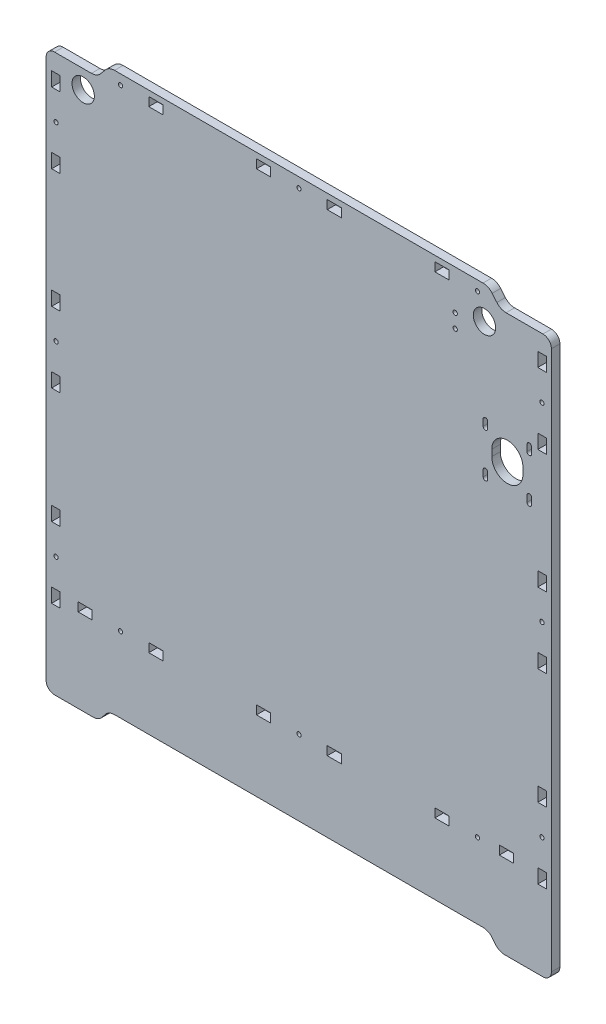
SolidWorks part; units mm, degrees
ref_plane "Спереди" through (0, 0, 0) normal (0, 0, 1) x (1, 0, 0)
ref_plane "Сверху" through (0, 0, 0) normal (0, 1, 0) x (1, 0, 0)
ref_plane "Справа" through (0, 0, 0) normal (1, 0, 0) x (0, 0, -1)
sketch "Эскиз1" plane through (0, 0, 0) normal (0, 0, 1) x (1, 0, 0)
  line L0 (133.6555, 83.4698) -> (133.6555, 87.9698)
  line L1 (133.6555, 118.9698) -> (133.6555, 114.4698)
  line L2 (130.4555, 83.4698) -> (130.4555, 87.9698)
  line L3 (158.5555, 98.9698) -> (158.5555, 103.4698)
  line L4 (130.4555, 118.9698) -> (130.4555, 114.4698)
  line L5 (161.4555, 118.9698) -> (161.4555, 114.4698)
  line L6 (164.6555, 118.9698) -> (164.6555, 114.4698)
  line L7 (136.5555, 98.9698) -> (136.5555, 103.4698)
  line L8 (161.4555, 83.4698) -> (161.4555, 87.9698)
  line L9 (164.6555, 83.4698) -> (164.6555, 87.9698)
  line L10 (-174.3451, 35.4216) -> (-174.3451, 45.4216)
  line L11 (106.3726, -142.2004) -> (96.3778, -142.2004)
  line L12 (96.3778, -142.2004) -> (96.3778, -136.0006)
  line L13 (96.3778, -136.0006) -> (106.3726, -136.0006)
  line L14 (106.3726, -136.0006) -> (106.3726, -142.2004)
  line L15 (151.7592, -142.2004) -> (141.91, -142.2004)
  line L16 (141.91, -142.2004) -> (141.91, -136.0006)
  line L17 (141.91, -136.0006) -> (151.7592, -136.0006)
  line L18 (151.7592, -136.0006) -> (151.7592, -142.2004)
  line L19 (-19.7199, 191.9054) -> (-29.6916, 191.9054)
  line L20 (-29.6916, 191.9054) -> (-29.6916, 198.1051)
  line L21 (-29.6916, 198.1051) -> (-19.7199, 198.1051)
  line L22 (-19.7199, 198.1051) -> (-19.7199, 191.9054)
  line L23 (30.2801, 191.9054) -> (20.3037, 191.9054)
  line L24 (20.3037, 191.9054) -> (20.3037, 198.1051)
  line L25 (20.3037, 198.1051) -> (30.2801, 198.1051)
  line L26 (30.2801, 198.1051) -> (30.2801, 191.9054)
  line L27 (-145.8164, -142.2004) -> (-155.6656, -142.2004)
  line L28 (-155.6656, -142.2004) -> (-155.6656, -136.0006)
  line L29 (-155.6656, -136.0006) -> (-145.8164, -136.0006)
  line L30 (-145.8164, -136.0006) -> (-145.8164, -142.2004)
  line L31 (-95.8164, -142.2004) -> (-105.7664, -142.2004)
  line L32 (-105.7664, -142.2004) -> (-105.7664, -136.0006)
  line L33 (-105.7664, -136.0006) -> (-95.8164, -136.0006)
  line L34 (-95.8164, -136.0006) -> (-95.8164, -142.2004)
  line L35 (-19.722, -142.199) -> (-29.6916, -142.199)
  line L36 (-29.6916, -142.199) -> (-29.6916, -135.9992)
  line L37 (-29.6916, -135.9992) -> (-19.722, -135.9992)
  line L38 (-19.722, -135.9992) -> (-19.722, -142.199)
  line L39 (30.2781, -142.199) -> (20.3037, -142.199)
  line L40 (20.3037, -142.199) -> (20.3037, -135.9992)
  line L41 (20.3037, -135.9992) -> (30.2781, -135.9992)
  line L42 (30.2781, -135.9992) -> (30.2781, -142.199)
  line L43 (-174.3451, 45.4216) -> (-168.4387, 45.4216)
  line L44 (-168.4387, 45.4216) -> (-168.4387, 35.4216)
  line L45 (-168.4387, 35.4216) -> (-174.3451, 35.4216)
  line L46 (-174.4387, -14.5784) -> (-174.4387, -4.5784)
  line L47 (-174.4387, -4.5784) -> (-168.4387, -4.5784)
  line L48 (-168.4387, -4.5784) -> (-168.4387, -14.5784)
  line L49 (-168.4387, -14.5784) -> (-174.4387, -14.5784)
  line L50 (-174.3451, 169.5931) -> (-174.3451, 179.5931)
  line L51 (-174.3451, 179.5931) -> (-168.4387, 179.5931)
  line L52 (-168.4387, 179.5931) -> (-168.4387, 169.5931)
  line L53 (-168.4387, 169.5931) -> (-174.3451, 169.5931)
  line L54 (-174.3451, 119.5932) -> (-174.3451, 129.5932)
  line L55 (-174.3451, 129.5932) -> (-168.4387, 129.5932)
  line L56 (-168.4387, 129.5932) -> (-168.4387, 119.5932)
  line L57 (-168.4387, 119.5932) -> (-174.3451, 119.5932)
  line L58 (-174.4387, -96.2996) -> (-174.4387, -86.2996)
  line L59 (-174.4387, -86.2996) -> (-168.4387, -86.2996)
  line L60 (-168.4387, -86.2996) -> (-168.4387, -96.2996)
  line L61 (-168.4387, -96.2996) -> (-174.4387, -96.2996)
  line L62 (-174.4387, -146.2996) -> (-174.4387, -136.2996)
  line L63 (-174.4387, -136.2996) -> (-168.4387, -136.2996)
  line L64 (-168.4387, -136.2996) -> (-168.4387, -146.2996)
  line L65 (-168.4387, -146.2996) -> (-174.4387, -146.2996)
  line L66 (169.0555, 35.4216) -> (169.0555, 45.4216)
  line L67 (169.0555, 45.4216) -> (175.077, 45.4216)
  line L68 (175.077, 45.4216) -> (175.077, 35.4216)
  line L69 (175.077, 35.4216) -> (169.0555, 35.4216)
  line L70 (169.0555, -14.5784) -> (169.0555, -4.5784)
  line L71 (169.0555, -4.5784) -> (175.077, -4.5784)
  line L72 (175.077, -4.5784) -> (175.077, -14.5784)
  line L73 (175.077, -14.5784) -> (169.0555, -14.5784)
  line L74 (169.0555, -96.2996) -> (169.0555, -86.2996)
  line L75 (169.0555, -86.2996) -> (175.077, -86.2996)
  line L76 (175.077, -86.2996) -> (175.077, -96.2996)
  line L77 (175.077, -96.2996) -> (169.0555, -96.2996)
  line L78 (169.0555, -146.2996) -> (169.0555, -136.2996)
  line L79 (169.0555, -136.2996) -> (175.077, -136.2996)
  line L80 (175.077, -136.2996) -> (175.077, -146.2996)
  line L81 (175.077, -146.2996) -> (169.0555, -146.2996)
  line L82 (169.0555, 169.7437) -> (169.0555, 179.5931)
  line L83 (169.0555, 179.5931) -> (175.0673, 179.5931)
  line L84 (175.0673, 169.7437) -> (169.0555, 169.7437)
  line L85 (169.0555, 119.5932) -> (169.0555, 129.5932)
  line L86 (169.0555, 129.5932) -> (175.0673, 129.5932)
  line L87 (175.0673, 129.5932) -> (175.0673, 119.5932)
  line L88 (175.0673, 119.5932) -> (169.0555, 119.5932)
  line L89 (-105.7664, 198.1027) -> (-95.7933, 198.1027)
  line L90 (-95.7933, 198.1027) -> (-95.7933, 191.903)
  line L91 (-95.7933, 191.903) -> (-105.7664, 191.903)
  line L92 (-105.7664, 191.903) -> (-105.7664, 198.1027)
  line L93 (106.3778, 191.903) -> (106.177, 191.9198)
  line L94 (96.3778, 191.903) -> (96.3778, 198.1027)
  line L95 (106.3778, 198.1027) -> (106.3778, 191.903)
  line L96 (146.6406, 192.0194) -> (172.677, 192.0194)
  line L97 (106.177, 191.9198) -> (96.3778, 191.903)
  line L98 (-146.2866, 192.0194) -> (-172.323, 192.0194)
  line L99 (-136.4794, 198.9835) -> (-139.7752, 195.0557)
  line L100 (130.322, 202.0198) -> (-129.968, 202.0198)
  line L101 (136.8334, 198.9835) -> (140.1292, 195.0557)
  line L102 (175.077, 169.8198) -> (175.0673, 169.7437)
  line L103 (106.177, 198.1198) -> (106.3778, 198.1027)
  line L104 (96.3778, 198.1027) -> (106.177, 198.1198)
  line L105 (175.0673, 179.5931) -> (175.077, 169.8198)
  line L106 (139.1292, -198.2549) -> (136.8334, -195.2353)
  line L107 (-129.968, -192.199) -> (130.322, -192.199)
  line L108 (-172.323, -201.2912) -> (-145.2866, -201.2912)
  line L109 (-138.7752, -198.2549) -> (-136.4794, -195.2353)
  line L110 (172.677, -201.2912) -> (145.6406, -201.2912)
  line L111 (-178.323, 186.0194) -> (-178.323, -195.2912)
  line L112 (178.677, 186.0194) -> (178.677, -195.2912)
  arc A0 (158.5555, 103.4698) -> (136.5555, 103.4698) centre (147.5555, 103.4698) ccw
  arc A1 (161.4555, 83.4698) -> (164.6555, 83.4698) centre (163.0555, 83.4698) ccw
  arc A2 (136.5555, 98.9698) -> (158.5555, 98.9698) centre (147.5555, 98.9698) ccw
  arc A3 (130.4555, 83.4698) -> (133.6555, 83.4698) centre (132.0555, 83.4698) ccw
  arc A4 (164.6555, 87.9698) -> (161.4555, 87.9698) centre (163.0555, 87.9698) ccw
  circle A5 centre (110.677, 164.3198) radius 1.55
  circle A6 centre (110.677, 174.0198) radius 1.55
  arc A7 (130.4555, 114.4698) -> (133.6555, 114.4698) centre (132.0555, 114.4698) ccw
  arc A8 (133.6555, 118.9698) -> (130.4555, 118.9698) centre (132.0555, 118.9698) ccw
  arc A9 (164.6555, 118.9698) -> (161.4555, 118.9698) centre (163.0555, 118.9698) ccw
  arc A10 (161.4555, 114.4698) -> (164.6555, 114.4698) centre (163.0555, 114.4698) ccw
  arc A11 (133.6555, 87.9698) -> (130.4555, 87.9698) centre (132.0555, 87.9698) ccw
  circle A12 centre (131.377, 179.0198) radius 7.9
  circle A13 centre (-152.123, 179.0198) radius 7.9
  arc A14 (-129.968, 202.0198) -> (-136.4794, 198.9835) centre (-129.968, 193.5198) ccw
  arc A15 (-146.2866, 192.0194) -> (-139.7752, 195.0557) centre (-146.2866, 200.5194) ccw
  arc A16 (-172.323, 192.0194) -> (-178.323, 186.0194) centre (-172.323, 186.0194) ccw
  arc A17 (140.1292, 195.0557) -> (146.6406, 192.0194) centre (146.6406, 200.5194) ccw
  arc A18 (136.8334, 198.9835) -> (130.322, 202.0198) centre (130.322, 193.5198) ccw
  arc A19 (178.677, 186.0194) -> (172.677, 192.0194) centre (172.677, 186.0194) ccw
  arc A20 (136.8334, -195.2353) -> (130.322, -192.199) centre (130.322, -200.699) ccw
  arc A21 (-178.323, -195.2912) -> (-172.323, -201.2912) centre (-172.323, -195.2912) ccw
  arc A22 (-145.2866, -201.2912) -> (-138.7752, -198.2549) centre (-145.2866, -192.7912) ccw
  arc A23 (139.1292, -198.2549) -> (145.6406, -201.2912) centre (145.6406, -192.7912) ccw
  arc A24 (-129.968, -192.199) -> (-136.4794, -195.2353) centre (-129.968, -200.699) ccw
  circle A25 centre (-171.2415, 149.647) radius 1.5
  arc A26 (172.677, -201.2912) -> (178.677, -195.2912) centre (172.677, -195.2912) ccw
  circle A27 centre (-171.2415, 15.5735) radius 1.5
  circle A28 centre (171.9877, 149.6742) radius 1.5
  circle A29 centre (126.4621, 195.0571) radius 1.5
  circle A30 centre (-125.7107, 195.0571) radius 1.5
  circle A31 centre (0.3581, 195.0571) radius 1.5
  circle A32 centre (-125.7495, -139.0659) radius 1.5
  circle A33 centre (-171.2415, -116.2123) radius 1.5
  circle A34 centre (0.3757, -139.0659) radius 1.5
  circle A35 centre (126.4428, -139.0659) radius 1.5
  circle A36 centre (171.9877, -116.2123) radius 1.5
  circle A37 centre (171.9877, 15.5093) radius 1.5
extrude "Бобышка-Вытянуть1" add sketch "Эскиз1" along normal blind 6
